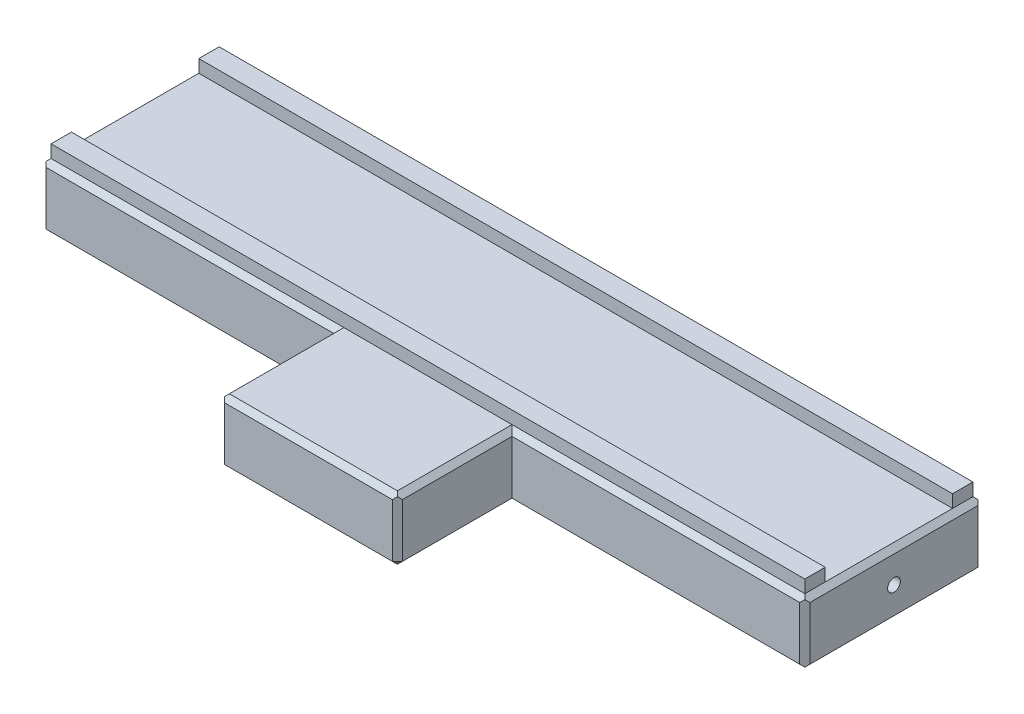
SolidWorks part; units mm, degrees
material "POM Acetal Copolymer"
ref_plane "Front Plane" through (0, 0, 0) normal (0, 0, 1) x (1, 0, 0)
ref_plane "Top Plane" through (0, 0, 0) normal (0, 1, 0) x (1, 0, 0)
ref_plane "Right Plane" through (0, 0, 0) normal (1, 0, 0) x (0, 0, -1)
sketch "Sketch1" plane through (0, 0, 0) normal (0, 1, 0) x (1, 0, 0)
  line L1 (-36.4733, 21.3189) -> (39.7267, 21.3189)
  line L2 (-36.4733, 21.3189) -> (-36.4733, 3.5389)
  line L3 (-36.4733, 3.5389) -> (39.7267, 3.5389)
  line L4 (39.7267, 21.3189) -> (39.7267, 3.5389)
  dimension "D1" = 76.2
  dimension "D2" = 17.78
extrude "Boss-Extrude1" add sketch "Sketch1" along normal blind 6.35
sketch "Sketch2" plane through (0, 0, -3.5389) normal (0, 0, 1) x (1, 0, 0)
  line L0 (-36.4733, 6.35) -> (39.7267, 6.35) construction
  line L1 (-7.2633, 6.35) -> (10.5167, 6.35)
  line L2 (-7.2633, 6.35) -> (-7.2633, 0)
  line L3 (-7.2633, 0) -> (10.5167, 0)
  line L4 (10.5167, 6.35) -> (10.5167, 0)
  line L5 (-36.4733, 0) -> (39.7267, 0) construction
  line L6 (-36.4733, 6.35) -> (-36.4733, 0) construction
  line L7 (39.7267, 6.35) -> (39.7267, 0) construction
  dimension "D1" = 17.78
  dimension "D2" = 29.21
  dimension "D3" = 29.21
extrude "Boss-Extrude2" add sketch "Sketch2" along normal blind 11.43
sketch "Sketch3" plane through (0, 6.35, 0) normal (0, 1, 0) x (1, 0, 0)
  line L0 (-36.4733, 21.3189) -> (-36.4733, 3.5389) construction
  line L1 (-35.9653, 20.8109) -> (39.2187, 20.8109)
  line L2 (-35.9653, 20.8109) -> (-35.9653, 18.7789)
  line L3 (-35.9653, 18.7789) -> (39.2187, 18.7789)
  line L4 (39.2187, 20.8109) -> (39.2187, 18.7789)
  line L5 (39.7267, 21.3189) -> (-36.4733, 21.3189) construction
  line L6 (-36.4733, 12.4289) -> (39.7267, 12.4289) construction
  line L7 (39.7267, 3.5389) -> (39.7267, 21.3189) construction
  line L8 (-35.9653, 6.0789) -> (39.2187, 6.0789)
  line L9 (39.2187, 4.0469) -> (39.2187, 6.0789)
  line L10 (-35.9653, 4.0469) -> (39.2187, 4.0469)
  line L11 (-35.9653, 4.0469) -> (-35.9653, 6.0789)
  dimension "D1" = 75.184
  dimension "D2" = 0.508
  dimension "D3" = 2.032
  dimension "D4" = 0.508
extrude "Boss-Extrude3" add sketch "Sketch3" along normal blind 1.27
sketch "Sketch4" plane through (0, 0, -21.3189) normal (0, 0, -1) x (-1, 0, 0)
  line L0 (-1.6267, 6.35) -> (-1.6267, 0) construction
  line L1 (-39.7267, 6.35) -> (36.4733, 6.35) construction
  line L2 (-39.7267, 0) -> (36.4733, 0) construction
  circle A0 centre (-1.6267, 3.175) radius 2.286
  dimension "D1" = 4.572
extrude "Cut-Extrude1" cut sketch "Sketch4" against normal blind 1.778
sketch "Sketch5" plane through (0, 0, -19.5409) normal (0, 0, -1) x (-1, 0, 0)
  circle A0 centre (-1.6267, 3.175) radius 1.1811
  dimension "D1" = 2.3622
extrude "Cut-Extrude2" cut sketch "Sketch5" against normal blind 1.27
sketch "Sketch6" plane through (-36.4733, 0, 0) normal (-1, 0, 0) x (0, 0, 1)
  line L0 (-3.5389, 6.35) -> (-3.5389, 0) construction
  line L1 (-21.3189, 6.35) -> (-3.5389, 6.35) construction
  circle A0 centre (-12.4289, 3.175) radius 0.635
  dimension "D3" = 1.27
  dimension "D1" = 8.89
  dimension "D2" = 3.175
extrude "Cut-Extrude3" cut sketch "Sketch6" against normal through all
chamfer "Chamfer1" distance 0.508 angle 45 8 edges at (1.6267, 6.35, -21.3189) (1.6267, 0, -21.3189) (25.1217, 0, -3.5389) (-21.8683, 0, -3.5389) (10.5167, 6.35, 2.1761) (25.1217, 6.35, -3.5389) (-7.2633, 6.35, 2.1761) (-21.8683, 6.35, -3.5389)
chamfer "Chamfer2" distance 0.508 angle 45 14 edges at (-36.4733, 0, -12.4289) (-36.4733, 3.175, -3.5389) (-36.4733, 6.35, -12.4289) (-36.4733, 3.175, -21.3189) (39.7267, 3.175, -21.3189) (39.7267, 3.175, -3.5389) (39.7267, 0, -12.4289) (39.7267, 6.35, -12.4289) (1.6267, 6.35, 7.8911) (10.5167, 2.921, 7.8911) (-7.2633, 2.921, 7.8911) (10.5167, 0, 1.9221) (1.6267, 0, 7.8911) (-7.2633, 0, 1.9221)
